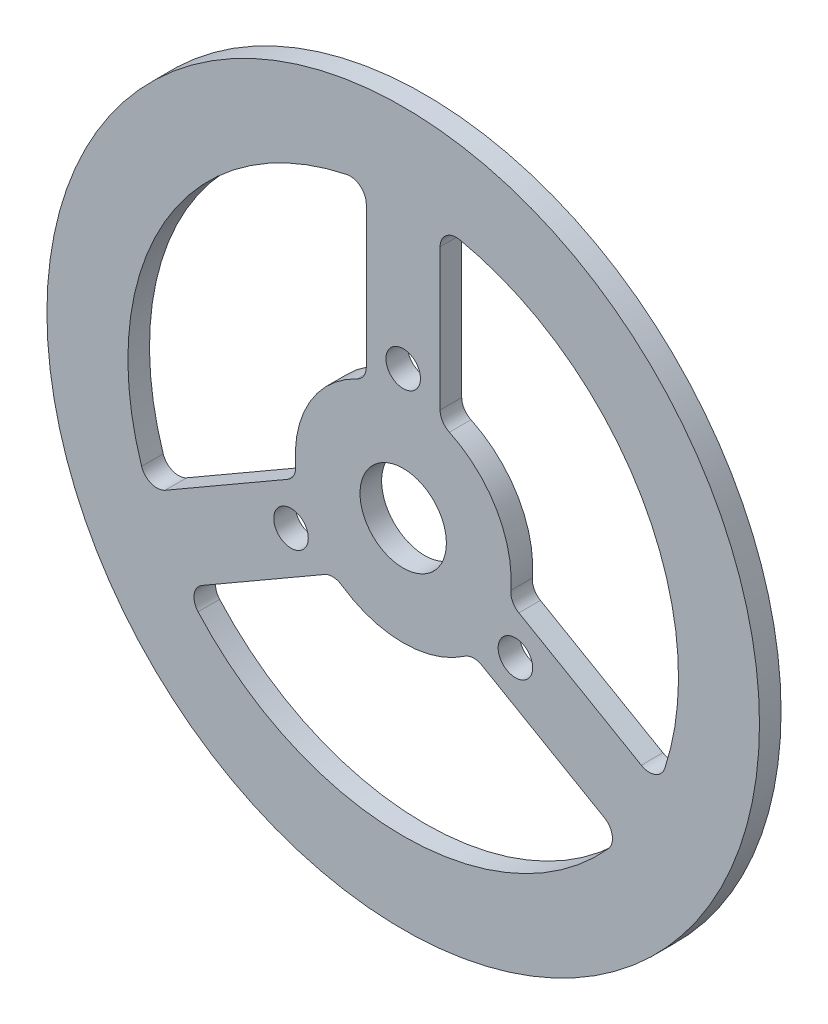
SolidWorks part; units mm, degrees
material "Thornel Mat VMA"
ref_plane "Front Plane" through (0, 0, 0) normal (0, 0, 1) x (1, 0, 0)
ref_plane "Top Plane" through (0, 0, 0) normal (0, 1, 0) x (1, 0, 0)
ref_plane "Right Plane" through (0, 0, 0) normal (1, 0, 0) x (0, 0, -1)
sketch "Sketch1" plane through (0, 0, 0) normal (0, 0, 1) x (1, 0, 0)
  circle A0 centre (0, 0) radius 33
  circle A1 centre (0, 0) radius 4 construction
  circle A2 centre (0, 0) radius 4
  dimension "D1" = 66
extrude "Boss-Extrude1" add sketch "Sketch1" along normal blind 2
sketch "Sketch3" plane through (0, 0, 2) normal (0, 0, 1) x (1, 0, 0)
  line L1 (0, 12) -> (-10.3923, -6) construction
  line L2 (-10.3923, -6) -> (10.3923, -6) construction
  line L3 (10.3923, -6) -> (0, 12) construction
  circle A0 centre (0, 0) radius 6 construction
  circle A1 centre (0, 0) radius 12 construction
  circle A2 centre (0, 12) radius 1.6
  circle A3 centre (-10.3923, -6) radius 1.6
  circle A4 centre (10.3923, -6) radius 1.6
  dimension "D1" = 24
  dimension "D2" = 3.2
extrude "Cut-Extrude1" cut sketch "Sketch3" against normal blind 10
sketch "Sketch4" plane through (0, 0, 2) normal (0, 0, 1) x (1, 0, 0)
  line L0 (8.7215, 23.9622) -> (0, 0) construction
  line L1 (0, 0) -> (25.1126, -4.428) construction
  line L2 (0, 12) -> (0, 0) construction
  line L3 (10.3923, -6) -> (0, 0) construction
  line L4 (3.4202, 9.3969) -> (3.4202, 25.2696)
  line L5 (9.8481, -1.7365) -> (23.5942, -9.6728)
  circle A0 centre (0, 0) radius 25.5
  circle A1 centre (0, 0) radius 10
  dimension "D1" = 20
  dimension "D2" = 51
  dimension "D3" = 20
  dimension "D4" = 20
extrude "Cut-Extrude2" cut sketch "Sketch4" against normal blind 10 contours A1 L1 A0 L0 region at (14.5691, 8.4115, 2)
fillet "Fillet1" radius 1.5 4 edges at (23.5942, -9.6728, 1) (9.8481, -1.7365, 1) (3.4202, 9.3969, 1) (3.4202, 25.2696, 1)
pattern_circular "CirPattern1" count 3 every 120 about axis through (0, 0, 2) along (0, 0, 1) of "Fillet1", "Cut-Extrude2"
